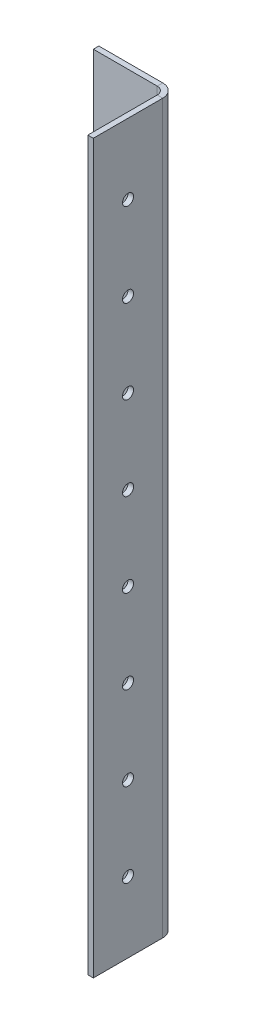
SolidWorks part; units mm, degrees
note: The reader was unsure of these and kept them because the rebuilt part matched: flange length of "Edge-Flange1".
material "Plain Carbon Steel"
ref_plane "Front Plane" through (0, 0, 0) normal (0, 0, 1) x (1, 0, 0)
ref_plane "Top Plane" through (0, 0, 0) normal (0, 1, 0) x (1, 0, 0)
ref_plane "Right Plane" through (0, 0, 0) normal (1, 0, 0) x (0, 0, -1)
sketch "Sketch1" plane through (0, 0, 0) normal (0, 0, 1) x (1, 0, 0)
  line L1 (-70, -660) -> (70, -660)
  line L2 (-70, -660) -> (-70, 660)
  line L3 (-70, 660) -> (70, 660)
  line L4 (70, -660) -> (70, 660)
  line L5 (-70, -660) -> (70, 660) construction
  line L6 (-70, 660) -> (70, -660) construction
  point P0 (0, 0)
  dimension "D1" = 1320
  dimension "D2" = 140
base flange "Base-Flange1" sketch "Sketch1" thickness 10 reverse thickness direction no parameters "D1"=3
edge flange "Edge-Flange1" sketch "Sketch10" flange angle 90 flange length 150 flange position material inside bend radius 14 thickness 10 relief rectangular parameters "D6"=10, "D8"=1
sketch "Sketch10" plane through (70, 0, 0) normal (1, 0, 0) x (0, 1, 0)
  line L2 (-660, 0) -> (-660, 140)
  line L3 (-660, 140) -> (660, 140)
  line L4 (660, 140) -> (660, 0)
  line L7 (-660, 0) -> (660, 0) construction
  line L8 (-660, 0) -> (660, 0)
bend "EdgeBend1" bend radius 14 bend angle 90 parameters "D5"=1
sketch "Sketch12" plane through (60, 0, 0) normal (-1, 0, 0) x (0, 0, 1)
  line L0 (140, 660) -> (0, 660) construction
  line L3 (14, 660) -> (140, 660) construction
  circle A0 centre (77, 532) radius 10
  point P10 (77, 660)
  dimension "D1" = 20
  dimension "D2" = 128
extrude "Cut-Extrude1" cut sketch "Sketch12" against normal blind 10
sketch "Sketch13" plane through (0, 0, 0) normal (0, 0, 1) x (1, 0, 0)
  line L0 (-70, 660) -> (-70, -660) construction
  line L1 (46, 660) -> (-70, 660) construction
  circle A0 centre (-7, 532) radius 10
  dimension "D1" = 20
  dimension "D2" = 128
  dimension "D3" = 63
extrude "Cut-Extrude2" cut sketch "Sketch13" against normal blind 10
pattern_linear "LPattern1" count 8 spacing 152 along (0, -1, 0) of "Cut-Extrude2", "Cut-Extrude1"
sketch "Bend-Lines1" [suppressed] plane through (0, 0, 0) normal (0, 1, 0) x (1, 0, 0)
sketch "Bounding-Box1" [suppressed] plane through (0, 0, 0) normal (0, 1, 0) x (1, 0, 0)
sheet metal parameters "Sheet-Metal1" thickness 10 parameters "D1"=3
flat pattern "Flat-Pattern1" [suppressed]
sketch "Bend-Lines2" plane through (0, 0, 0) normal (0, 1, 0) x (1, 0, 0)
sketch3d "Bounding-Box2" [suppressed]
  line L0 (-100, 950, 0) -> (-100, -950, 0) construction
  line L1 (100, 950, 0) -> (100, -950, 0) construction
  line L2 (-100, 950, 0) -> (100, 950, 0) construction
  line L3 (-100, -950, 0) -> (100, -950, 0) construction
sheet metal parameters "Sheet-Metal2" thickness 10 parameters "D1"=3
flat pattern "Flat-Pattern1"
sketch "Bend-Lines2" plane through (0, 0, 0) normal (0, 0, 1) x (1, 0, 0)
  line L1 (65.9226, -650) -> (65.9226, 650) construction
  line L3 (65.9226, -650) -> (65.9226, 650) construction
sketch3d "Bounding-Box2" [suppressed]
  line L0 (206.8451, 650, 0) -> (206.8451, -650, 0) construction
  line L1 (-75, 650, 0) -> (-75, -650, 0) construction
  line L2 (206.8451, 650, 0) -> (-75, 650, 0) construction
  line L3 (206.8451, -650, 0) -> (-75, -650, 0) construction
bend of the flat pattern "Flatten-<EdgeBend1>1"
sheet metal parameters "Sheet-Metal3" thickness 10 parameters "D1"=3
flat pattern "Flat-Pattern1"
sketch "Bend-Lines2" plane through (0, 0, 0) normal (0, 0, 1) x (1, 0, 0)
  line L1 (65.9226, -650) -> (65.9226, 650) construction
  line L3 (65.9226, -650) -> (65.9226, 650) construction
sketch3d "Bounding-Box2" [suppressed]
  line L0 (206.8451, 650, 0) -> (206.8451, -650, 0) construction
  line L1 (-75, 650, 0) -> (-75, -650, 0) construction
  line L2 (206.8451, 650, 0) -> (-75, 650, 0) construction
  line L3 (206.8451, -650, 0) -> (-75, -650, 0) construction
bend of the flat pattern "Flatten-<EdgeBend1>1"
sheet metal parameters "Sheet-Metal4" thickness 10 parameters "D1"=3
flat pattern "Flat-Pattern1"
sketch "Bend-Lines2" plane through (0, 0, 0) normal (0, 0, 1) x (1, 0, 0)
  line L1 (65.9226, -650) -> (65.9226, 650) construction
  line L3 (65.9226, -650) -> (65.9226, 650) construction
sketch3d "Bounding-Box2" [suppressed]
  line L0 (206.8451, 650, 0) -> (206.8451, -650, 0) construction
  line L1 (-75, 650, 0) -> (-75, -650, 0) construction
  line L2 (206.8451, 650, 0) -> (-75, 650, 0) construction
  line L3 (206.8451, -650, 0) -> (-75, -650, 0) construction
bend of the flat pattern "Flatten-<EdgeBend1>1"
sheet metal parameters "Sheet-Metal5" thickness 10 parameters "D1"=3
flat pattern "Flat-Pattern1"
sketch "Bend-Lines2" plane through (0, 0, 0) normal (0, 0, 1) x (1, 0, 0)
  line L1 (60.9226, -660) -> (60.9226, 660) construction
  line L3 (60.9226, -660) -> (60.9226, 660) construction
sketch3d "Bounding-Box2" [suppressed]
  line L0 (201.8451, 660, 0) -> (201.8451, -660, 0) construction
  line L1 (-70, 660, 0) -> (-70, -660, 0) construction
  line L2 (201.8451, 660, 0) -> (-70, 660, 0) construction
  line L3 (201.8451, -660, 0) -> (-70, -660, 0) construction
bend of the flat pattern "Flatten-<EdgeBend1>1"
